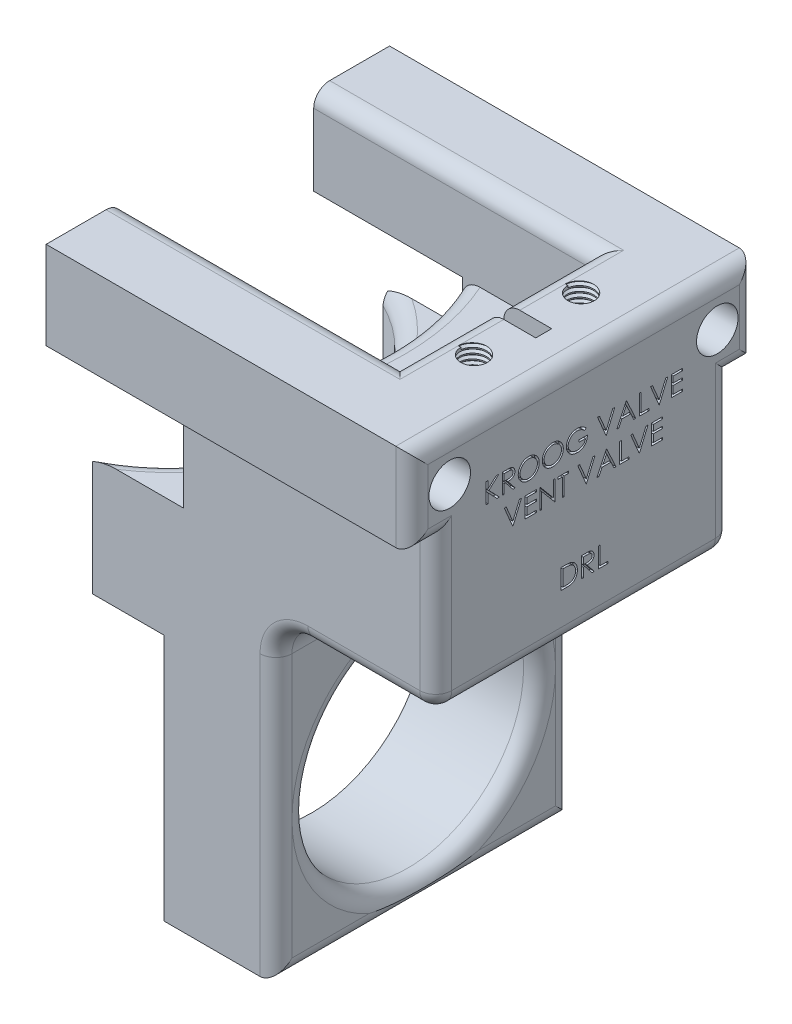
SolidWorks part; units mm, degrees
material "ABS"
ref_plane "Front Plane" through (0, 0, 0) normal (0, 0, 1) x (1, 0, 0)
ref_plane "Top Plane" through (0, 0, 0) normal (0, 1, 0) x (1, 0, 0)
ref_plane "Right Plane" through (0, 0, 0) normal (1, 0, 0) x (0, 0, -1)
sketch "Sketch2" plane through (0, 0, 0) normal (1, 0, 0) x (0, 0, -1)
  line L7 (-23.495, -21.59) -> (23.495, -21.59)
  line L8 (-23.495, -21.59) -> (-23.495, 52.07)
  line L9 (-23.495, 66.04) -> (23.495, 66.04)
  line L10 (23.495, -21.59) -> (23.495, 52.07)
  line L11 (-23.495, 66.04) -> (-27.305, 66.04)
  line L13 (-23.495, 52.07) -> (-27.305, 52.07)
  line L14 (-27.305, 66.04) -> (-27.305, 52.07)
  line L15 (23.495, 66.04) -> (27.305, 66.04)
  line L17 (23.495, 52.07) -> (27.305, 52.07)
  line L18 (27.305, 66.04) -> (27.305, 52.07)
  circle A0 centre (0, 0) radius 18.415
  point P13 (0, -21.59)
  dimension "D1" = 36.83
  dimension "D2" = 21.59
  dimension "D3" = 46.99
  dimension "D4" = 87.63
  dimension "D5" = 13.97
  dimension "D6" = 3.81
extrude "Boss-Extrude1" add sketch "Sketch2" along normal blind 17.78
sketch "Sketch4" plane through (0, 0, 0) normal (-1, 0, 0) x (0, 0, 1)
  line L0 (-23.495, -21.59) -> (-23.495, 52.07) construction
  line L1 (-23.495, 17.78) -> (23.495, 17.78)
  line L2 (-23.495, 17.78) -> (-23.495, 52.07)
  line L4 (23.495, 17.78) -> (23.495, 52.07)
  line L5 (27.305, 66.04) -> (27.305, 52.07) construction
  line L6 (27.305, 52.07) -> (23.495, 52.07) construction
  line L7 (-23.495, 52.07) -> (-27.305, 52.07) construction
  line L8 (-27.305, 52.07) -> (-27.305, 66.04) construction
  line L9 (-27.305, 66.04) -> (27.305, 66.04) construction
  line L10 (27.305, 66.04) -> (27.305, 52.07)
  line L11 (27.305, 52.07) -> (23.495, 52.07)
  line L12 (-23.495, 52.07) -> (-27.305, 52.07)
  line L13 (-27.305, 52.07) -> (-27.305, 66.04)
  line L14 (-27.305, 66.04) -> (27.305, 66.04)
  line L15 (23.495, 52.07) -> (23.495, -21.59) construction
  dimension "D1" = 17.78
extrude "Boss-Extrude2" add sketch "Sketch4" along normal blind 11.43
sketch "Sketch5" plane through (0, 66.04, 0) normal (0, 1, 0) x (1, 0, 0)
  line L0 (0, 0) -> (-22.7305, 0) construction
  line L2 (-11.43, -27.305) -> (-11.43, 27.305) construction
  circle A0 centre (-22.7305, 0) radius 34.925
  circle A1 centre (-22.7305, 0) radius 25.4
  dimension "D2" = 69.85
  dimension "D3" = 50.8
  dimension "D1" = 11.3005
extrude "Cut-Extrude1" cut sketch "Sketch5" against normal blind 15.24 from offset 13.97 contours A1 A0 | A1 region at (-56.6676, 66.04, 0) region at (-22.7305, 66.04, 0) offset against normal yes
extrude "Cut-Extrude2" cut sketch "Sketch5<3>" against normal blind 38.1 from surface contours A1 region at (-22.7305, 66.04, 0) starting at face at (-1.8888, 36.83, 0)
sketch "Sketch5<3>" plane through (0, 66.04, 0) normal (0, 1, 0) x (1, 0, 0) same geometry as "Sketch5"
sketch "Sketch6" plane through (-11.43, 0, 0) normal (-1, 0, 0) x (0, 0, 1)
  line L4 (-27.305, 52.07) -> (27.305, 52.07)
  line L19 (-27.305, 52.07) -> (27.305, 52.07)
  line L23 (-27.305, 66.04) -> (-27.305, 52.07)
  line L25 (-27.305, 66.04) -> (-27.305, 52.07)
  line L27 (27.305, 52.07) -> (27.305, 66.04)
  line L28 (27.305, 52.07) -> (27.305, 66.04)
  line L29 (27.305, 66.04) -> (-27.305, 66.04)
  line L30 (27.305, 66.04) -> (-27.305, 66.04)
  dimension "D1" = 0
extrude "Boss-Extrude3" add sketch "Sketch6" along normal blind 3.5301
sketch "Sketch11" plane through (17.78, 0, 0) normal (1, 0, 0) x (0, 0, -1)
  line L0 (23.495, -21.59) -> (23.495, 52.07) construction
  line L2 (-23.495, 52.07) -> (-23.495, 27.94)
  line L3 (-23.495, 27.94) -> (23.495, 27.94)
  line L4 (23.495, 52.07) -> (23.495, 27.94)
  line L5 (-23.495, 52.07) -> (-23.495, -21.59) construction
  line L6 (23.495, 52.07) -> (27.305, 52.07) construction
  line L7 (27.305, 52.07) -> (27.305, 66.04) construction
  line L8 (-27.305, 52.07) -> (-23.495, 52.07) construction
  line L9 (-27.305, 66.04) -> (-27.305, 52.07) construction
  line L10 (27.305, 66.04) -> (-27.305, 66.04) construction
  line L11 (23.495, 52.07) -> (27.305, 52.07)
  line L12 (27.305, 52.07) -> (27.305, 66.04)
  line L13 (-27.305, 52.07) -> (-23.495, 52.07)
  line L14 (-27.305, 66.04) -> (-27.305, 52.07)
  line L15 (27.305, 66.04) -> (-27.305, 66.04)
  dimension "D1" = 38.1
extrude "Boss-Extrude4" add sketch "Sketch11" along normal blind 25.4
sketch "Sketch7" plane through (0, 66.04, 0) normal (0, 1, 0) x (1, 0, 0)
  line L1 (-14.9601, 15.24) -> (29.2359, 15.24)
  line L2 (-14.9601, 15.24) -> (-14.9601, -15.24)
  line L3 (-14.9601, -15.24) -> (29.2359, -15.24)
  line L4 (29.2359, 15.24) -> (29.2359, -15.24)
  line L5 (-14.9601, -27.305) -> (-14.9601, 27.305) construction
  point P6 (29.2359, 0)
  dimension "D1" = 30.48
  dimension "D2" = 44.196
extrude "Cut-Extrude3" cut sketch "Sketch7" against normal up to surface (13.97 mm away) up to face at (19.7631, 52.07, 0)
sketch "Sketch8" plane through (0, 66.04, 0) normal (0, 1, 0) x (1, 0, 0)
  line L0 (29.2359, -15.24) -> (29.2359, 15.24) construction
  line L1 (29.2359, -1.27) -> (36.8559, -1.27)
  line L2 (29.2359, -1.27) -> (29.2359, 1.27)
  line L3 (29.2359, 1.27) -> (36.8559, 1.27)
  line L4 (36.8559, -1.27) -> (36.8559, 1.27)
  point P6 (33.0459, -1.27)
  point P7 (29.2359, 0)
  dimension "D1" = 2.54
  dimension "D2" = 7.62
extrude "Cut-Extrude4" cut sketch "Sketch8" against normal blind 2.54
sketch "Sketch9" plane through (0, 66.04, 0) normal (0, 1, 0) x (1, 0, 0)
  line L0 (17.78, 23.495) -> (17.78, -23.495) construction
  line L1 (-14.9601, -23.495) -> (17.78, -23.495) construction
  line L2 (0, 0) -> (17.78, 0) construction
  line L4 (43.18, 27.305) -> (43.18, -27.305) construction
  circle A0 centre (34.29, -8.509) radius 1.27
  circle A1 centre (34.29, 8.509) radius 1.27
  point P0 (34.29, -8.509)
  point P9 (34.29, 8.509)
  dimension "D3" = 2.54
  dimension "D1" = 8.89
  dimension "D2" = 14.986
hole_wizard "Tap Drill for M5x0.8 Tap1" positions "Sketch9" profile "Sketch10" hole size "M5x0.8" standard "ANSI Metric"
sketch "Sketch10" plane through (34.29, 66.04, 8.509) normal (1, 0, 0) x (0, 0, 1)
  line L0 (0, 0) -> (0, 9.1358)
  line L1 (0, 9.1358) -> (2.1, 7.874)
  line L2 (2.1, 7.874) -> (2.1, 0)
  line L5 (2.1, 0) -> (0, 0)
  line L10 (0, 9.1358) -> (-2.1, 7.874) construction
  line L11 (0, -6.35) -> (0, 107.95) construction
  dimension "Hole Dia." = 4.2
  dimension "Hole Depth" = 7.874
  dimension "Drill Angle" = 118
fillet "Fillet3" radius 2.54 2 edges at (2.6695, 36.83, 0) (12.1945, 52.07, 0)
fillet "Fillet5" radius 5.08 1 edges at (17.78, 27.94, 0)
fillet "Fillet6" radius 2.54 16 edges at (33.02, 27.94, 23.495) (19.2679, 26.4521, 23.495) (33.02, 27.94, -23.495) (19.2679, 26.4521, -23.495) (17.78, -21.59, 0) (17.78, 0.635, 23.495) (17.78, 0.635, -23.495) (43.18, 40.005, -23.495) (43.18, 27.94, 0) (43.18, 40.005, 23.495) (43.18, 52.07, 25.4) (43.18, 59.055, 27.305) (43.18, 66.04, 0) (43.18, 59.055, -27.305) (43.18, 52.07, -25.4) (17.78, 0, -18.415)
fillet "Fillet7" radius 2.54 4 edges at (29.2359, 66.04, 8.255) (7.1379, 66.04, 15.24) (29.2359, 66.04, -8.255) (7.1379, 66.04, -15.24)
sketch "Sketch15" plane through (-14.9601, 0, 0) normal (-1, 0, 0) x (0, 0, 1)
  line L0 (-27.305, 59.055) -> (-15.24, 59.055) construction
  line L1 (-27.305, 66.04) -> (-27.305, 52.07) construction
  line L2 (-15.24, 52.07) -> (-15.24, 63.5) construction
  line L3 (-21.2725, 52.07) -> (-21.2725, 66.04) construction
  line L4 (-27.305, 52.07) -> (-15.24, 52.07) construction
  line L5 (-17.78, 66.04) -> (-27.305, 66.04) construction
  line L6 (0, 0) -> (0, 66.04) construction
  line L7 (1.27, 66.04) -> (-1.27, 66.04) construction
  circle A0 centre (-21.2725, 59.055) radius 3.302
  circle A1 centre (21.2725, 59.055) radius 3.302
  dimension "D1" = 6.604
extrude "Cut-Extrude7" cut sketch "Sketch15" against normal through all
sketch "Sketch16" plane through (43.18, 0, 0) normal (1, 0, 0) x (0, 0, -1)
  line L0 (-20.955, 53.34) -> (20.955, 53.34) construction
  line L1 (-20.955, 48.26) -> (20.955, 48.26) construction
  line L2 (-20.955, 54.61) -> (-20.955, 30.48) construction
  line L3 (20.955, 30.48) -> (20.955, 54.61) construction
  line L4 (-20.955, 35.56) -> (20.955, 35.56) construction
  line L5 (-20.955, 30.48) -> (20.955, 30.48) construction
  text T0 "KROOG VALVE"
  text T1 "VENT VALVE"
  text T2 "DRL"
  dimension "D1" = 5.08
  dimension "D2" = 12.7
  dimension "D3" = 5.08
extrude "Cut-Extrude8" cut sketch "Sketch16" against normal blind 0.635
thread "Thread1" pitch 0.8 method cut profile "Thread Profile1" start angle 0, offset 0.254, length 10, pitch 0.8, diameter 4.2
ref_plane "Plane1" through (32.19, 66.294, 8.509) normal (0, 0, 1) x (-1, 0, 0)
sketch "Thread Profile1" plane through (32.19, 66.294, 8.509) normal (0, 0, 1) x (-1, 0, 0)
  line L0 (0, 0) -> (0, 0.8) construction
  line L1 (0, 0) -> (0.433, 0.25)
  line L2 (0.433, 0.25) -> (0.433, 0.35)
  line L3 (0.433, 0.35) -> (0, 0.6)
  line L4 (0.433, 0.3) -> (0, 0.3) construction
  line L11 (0, 0) -> (0, 0.6)
  point P2 (0, 0)
  dimension "Pitch" = 0.8
  dimension "Profile_Angle" = 60
  dimension "Profile_Land" = 0.1
  dimension "Profile_Height" = 0.433
thread "Thread2" pitch 0.8 method cut profile "Thread Profile2" start angle 0, offset 0.254, length 10, pitch 0.8, diameter 4.2
ref_plane "Plane2" through (32.19, 66.294, -8.509) normal (0, 0, 1) x (-1, 0, 0)
sketch "Thread Profile2" plane through (32.19, 66.294, -8.509) normal (0, 0, 1) x (-1, 0, 0)
  line L0 (0, 0) -> (0, 0.8) construction
  line L1 (0, 0) -> (0.433, 0.25)
  line L2 (0.433, 0.25) -> (0.433, 0.35)
  line L3 (0.433, 0.35) -> (0, 0.6)
  line L4 (0.433, 0.3) -> (0, 0.3) construction
  line L11 (0, 0) -> (0, 0.6)
  point P2 (0, 0)
  dimension "Pitch" = 0.8
  dimension "Profile_Angle" = 60
  dimension "Profile_Land" = 0.1
  dimension "Profile_Height" = 0.433
